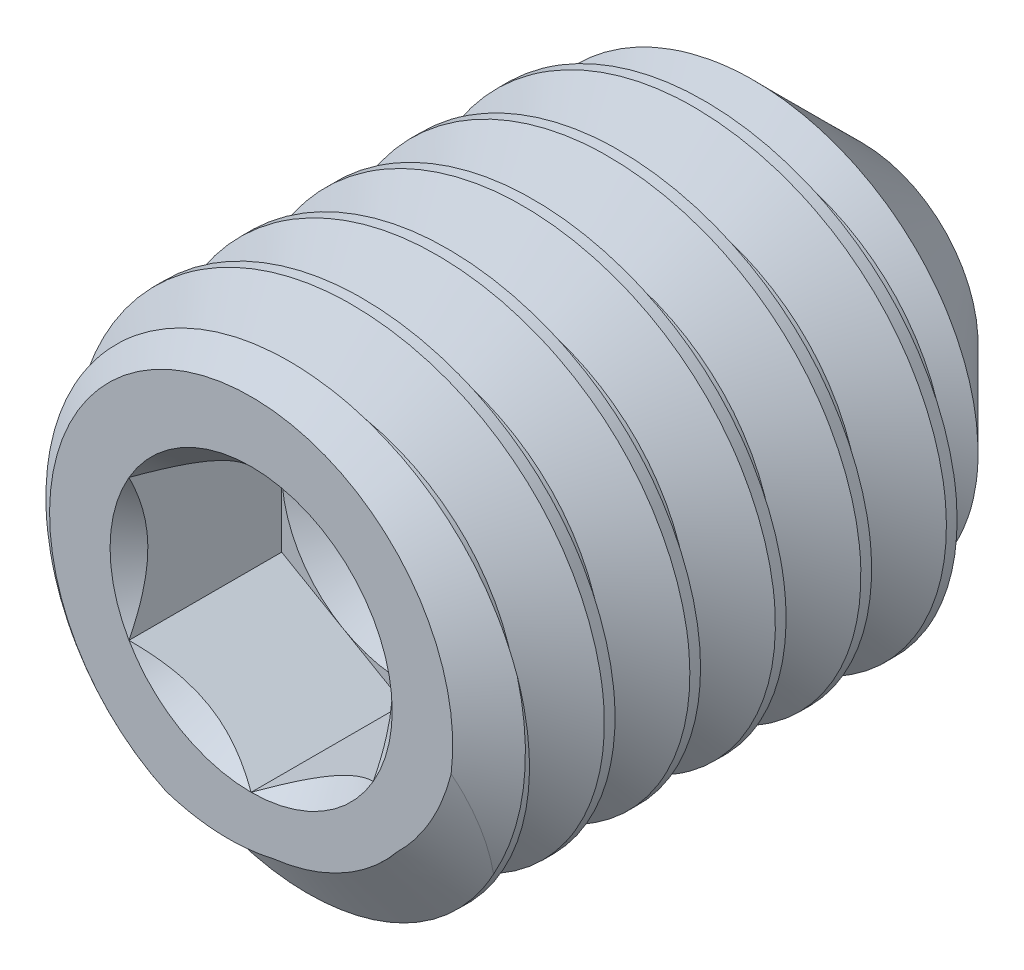
SolidWorks part; units mm, degrees
other "Imported1" parameters "D3"=5.5, "D1"=46.842, "Length"=5, "Drive Size"=2, "Thread Size"=4, "Thread Pitch"=0.7, "hex Depth"=1.25, "D2"=0.9112, "Dia"=12, "D4"=2.3829, "Cup Point Dia"=3.3528, "D5"=1.436, "D6"=1.4986, "D7"=5.0014, "Pitch"=1.75
ref_plane "Front" through (0, 0, 0) normal (0, 0, 1) x (1, 0, 0)
ref_plane "Top" through (0, 0, 0) normal (0, 1, 0) x (1, 0, 0)
ref_plane "Right" through (0, 0, 0) normal (1, 0, 0) x (0, 0, -1)
sketch "Sketch1" plane through (0, 0, 0) normal (1, 0, 0) x (0, 0, -1)
  line L0 (2.5, 2) -> (-2.5, 2) construction
  line L1 (-2.5, 2) -> (-2.5, -2) construction
  line L2 (-2.5, -2) -> (2.5, -2) construction
  line L3 (2.5, -2) -> (2.5, 2) construction
  line L4 (-2.5, 1) -> (-2.5, -1) construction
  line L5 (2.4562, 2.0758) -> (3.1562, 2.0758) construction
  line L6 (3.1562, 2.0758) -> (2.8062, 1.4696) construction
  line L7 (2.8062, 1.4696) -> (2.4562, 2.0758) construction
  line L8 (2.4781, 2.0379) -> (3.1344, 2.0379) construction
  line L9 (2.5, 2) -> (3.1125, 2) construction
  line L10 (2.8063, 2.0758) -> (2.8063, 2) construction
  line L11 (2.7625, 1.5453) -> (2.85, 1.5453) construction
  line L12 (2.8062, 1.5453) -> (2.8062, 1.4696) construction
  point P3 (0, 2)
  point P19 (2.8062, 2.0379)
  point P24 (-2.5, 0)
  point P25 (-2.5, 0)
  dimension "D1" = 0.0875
sketch "Sketch11" plane through (0, 0, 0) normal (1, 0, 0) x (0, 0, -1)
  line L0 (-2.5, 0) -> (-2.5, 1.65)
  line L1 (-2.5, 1.65) -> (-2.2549, 2)
  line L2 (-2.2549, 2) -> (1.45, 2)
  line L3 (1.45, 2) -> (2.5, 0.95)
  line L4 (2.5, 0.95) -> (1.9292, 0)
  line L5 (1.9292, 0) -> (-2.5, 0)
  line L6 (1.9292, 0) -> (2.5, 0) construction
  line L7 (2.5, 0) -> (2.5, 0.95) construction
  line L8 (2.5, -0.95) -> (1.9292, 0) construction
  line L9 (-2.2549, -2) -> (1.45, -2) construction
  line L10 (-2.5, -2) -> (2.5, -2) construction
  line L11 (-2.5, 2) -> (-2.5, -2) construction
  line L12 (2.5, -2) -> (2.5, 2) construction
  point P11 (0.05, -2)
  point P12 (-2.5, 2)
  dimension "D3" = 35
  dimension "D5" = 118
  dimension "D6" = 45
  dimension "D1" = 0.35
  dimension "D2" = 2.45
  dimension "D4" = 1.05
revolve "Revolve1" add sketch "Sketch11" angle 360 about L6
sketch "Sketch2" plane through (0, 0, 2.5) normal (0, 0, 1) x (1, 0, 0)
  line L1 (0, 1.1547) -> (-1, 0.5774)
  line L2 (-1, 0.5774) -> (-1, -0.5774)
  line L3 (-1, -0.5774) -> (0, -1.1547)
  line L4 (0, -1.1547) -> (1, -0.5774)
  line L5 (1, -0.5774) -> (1, 0.5774)
  line L6 (1, 0.5774) -> (0, 1.1547)
  circle A0 centre (0, 0) radius 1 construction
  circle A1 centre (0, 0) radius 2 construction
extrude "Cut-Extrude1" cut sketch "Sketch2" against normal blind 1.25
sketch "Sketch3" plane through (0, 0, 2.5) normal (0, 0, 1) x (1, 0, 0)
  circle A0 centre (0, 0) radius 1.1547
extrude "Cut-Extrude2" cut sketch "Sketch3" against normal through all draft 45
sketch "Sketch4" plane through (0, 0, 1.25) normal (0, 0, 1) x (1, 0, 0)
  circle A0 centre (0, 0) radius 1 construction
  circle A1 centre (0, 0) radius 1
extrude "Cut-Extrude3" cut sketch "Sketch4" against normal through all draft 60
sketch "Sketch13" plane through (0, 0, 0) normal (1, 0, 0) x (0, 0, -1)
  line L0 (0, -2) -> (0, 2) construction
  line L2 (-2.2549, 2) -> (1.45, 2) construction
  line L4 (1.9292, 0) -> (-2.5, 0) construction
  point P0 (-2.0708, 0)
  point P4 (0, 0)
  point P9 (2.0708, 0)
  dimension "D1" = 4
ref_plane "Plane1" through (0, 0, -2.5) normal (0, 0, 1) x (1, 0, 0)
sketch "Sketch5" plane through (0, 0, -2.5) normal (0, 0, 1) x (1, 0, 0)
  circle A0 centre (0, 0) radius 2 construction
  circle A1 centre (0, 0) radius 2
curve "Helix/Spiral1" pitch 0.7 height 5.5 radius 2 centre (0, 0, -2.5) axis (0, 0, 1) start towards (0, 1, 0)
sketch "Sketch6" plane through (0, 0, 0) normal (1, 0, 0) x (0, 0, -1)
  line L0 (2.4562, 2.0758) -> (3.1562, 2.0758) construction
  line L1 (3.1562, 2.0758) -> (2.8062, 1.4696) construction
  line L2 (2.8062, 1.4696) -> (2.4562, 2.0758) construction
  line L3 (2.8062, 2.0758) -> (2.8062, 2) construction
  line L4 (2.5, 2) -> (3.1125, 2) construction
  line L5 (2.8062, 1.5453) -> (2.8062, 1.4696) construction
  line L6 (2.7625, 1.5453) -> (2.4781, 2.0379)
  line L7 (2.4781, 2.0379) -> (3.1344, 2.0379)
  line L8 (2.4781, 2.0379) -> (3.1344, 2.0379) construction
  line L10 (2.7625, 1.5453) -> (2.85, 1.5453) construction
  line L12 (2.85, 1.5453) -> (2.7625, 1.5453)
  line L13 (3.1344, 2.0379) -> (2.85, 1.5453)
  point P9 (2.8062, 2)
  point P14 (2.8062, 2.0379)
  point P15 (2.8062, 2.0379)
  point P16 (2.8062, 1.5453)
  dimension "D1" = 0.7
  dimension "D2" = 0.0875
sweep "Cut-Sweep1" cut profiles "Sketch6" path "Helix/Spiral1"
equation "\"D3@Helix/Spiral1\" = \"Length@Sketch1\" * 1.1"
equation "\"hex Depth@Cut-Extrude1\" = \"Drive Size@Sketch1\" * .625"
equation "\"D1@Sketch6\" = \"Thread Pitch@Sketch1\""
equation "\"D2@Sketch6\" = \"D1@Sketch6\" / 8"
equation "\"D1@Sketch11\" = \"Thread Pitch@Sketch1\" * .5"
equation "\"D2@Sketch11\" = \"Thread Pitch@Sketch1\" * 3.5"
equation "\"D1@Helix/Spiral1\" = \"Thread Pitch@Sketch1\""
equation "\"D4@Sketch11\" = \"Thread Pitch@Sketch1\" * 1.5"
equation "\"D1@Sketch1\" = \"Thread Pitch@Sketch1\" / 8"
equation "\"D1@Sketch13\"=\"Thread Size@Sketch1\""
